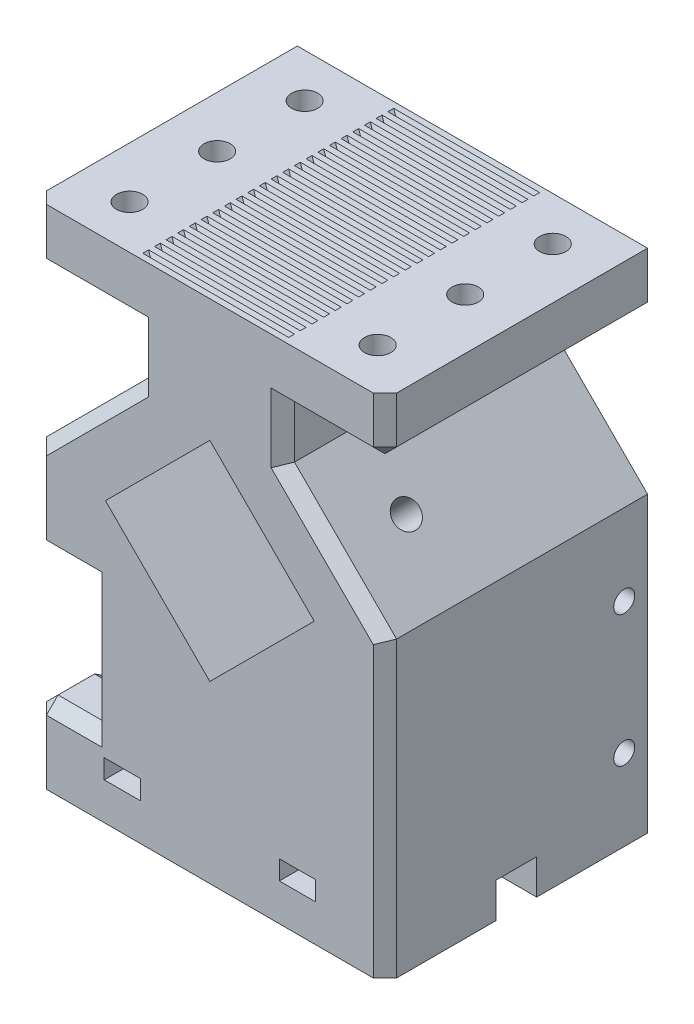
SolidWorks part; units mm, degrees
material "ABS"
ref_plane "Front Plane" through (0, 0, 0) normal (0, 0, 1) x (1, 0, 0)
ref_plane "Top Plane" through (0, 0, 0) normal (0, 1, 0) x (1, 0, 0)
ref_plane "Right Plane" through (0, 0, 0) normal (1, 0, 0) x (0, 0, -1)
sketch "Sketch1" plane through (0, 0, 0) normal (0, 0, 1) x (1, 0, 0)
  line L0 (-30, 25.15) -> (-12.5, 42.65)
  line L2 (30, 25.15) -> (30, -25.15)
  line L3 (30, -25.15) -> (-30, -25.15)
  line L4 (-30, 25.15) -> (-30, -25.15)
  line L5 (30, 25.15) -> (-30, -25.15) construction
  line L6 (30, -25.15) -> (-30, 25.15) construction
  line L7 (30, 25.15) -> (12.5, 42.65)
  line L8 (12.5, 42.65) -> (12.5, 51.65)
  line L9 (-12.5, 42.65) -> (-12.5, 51.65)
  line L10 (-12.5, 51.65) -> (12.5, 51.65) construction
  line L11 (-12.5, 51.65) -> (-30, 51.65)
  line L12 (-30, 51.65) -> (-30, 61.65)
  line L13 (-30, 61.65) -> (30, 61.65)
  line L14 (30, 61.65) -> (30, 51.65)
  line L15 (30, 51.65) -> (12.5, 51.65)
  point P0 (0, 0)
  dimension "D1" = 60
  dimension "D2" = 50.3
  dimension "D3" = 17.5
  dimension "D4" = 17.5
  dimension "D5" = 17.5
  dimension "D6" = 17.5
  dimension "D7" = 9
  dimension "D8" = 10
  dimension "D9" = 25.15
extrude "Boss-Extrude1" add sketch "Sketch1" along normal blind 45
sketch "Sketch2" plane through (0, 0, 45) normal (0, 0, 1) x (1, 0, 0)
  line L0 (0, 40.6296) -> (-17.8898, 22.7398)
  line L1 (-17.8898, 22.7398) -> (0, 4.85)
  line L2 (0, 4.85) -> (17.8898, 22.7398)
  line L3 (17.8898, 22.7398) -> (0, 40.6296)
  line L4 (0, 40.6296) -> (0, 0) construction
  line L5 (-30, -25.15) -> (30, -25.15) construction
  dimension "D1" = 25.3
  dimension "D2" = 25.3
  dimension "D3" = 30
extrude "Cut-Extrude1" cut sketch "Sketch2" against normal blind 25
sketch "Sketch3" plane through (0, -25.15, 0) normal (0, -1, 0) x (1, 0, 0)
  line L0 (-30, 26) -> (30, 26)
  line L1 (-30, 45) -> (-30, 0) construction
  line L2 (30, 45) -> (30, 0) construction
  line L3 (30, 26) -> (30, 19)
  line L4 (30, 19) -> (4.5, 19)
  line L5 (4.5, 19) -> (4.5, 3)
  line L6 (4.5, 3) -> (-4.5, 3)
  line L7 (-4.5, 3) -> (-4.5, 19)
  line L8 (-4.5, 19) -> (-30, 19)
  line L9 (-30, 19) -> (-30, 26)
  line L10 (0, 0) -> (0, 45) construction
  line L11 (-30, 0) -> (30, 0) construction
  line L12 (-30, 45) -> (30, 45) construction
  point P17 (0, 3)
  dimension "D1" = 9
  dimension "D2" = 7
  dimension "D3" = 16
  dimension "D4" = 19
extrude "Cut-Extrude2" cut sketch "Sketch3" against normal blind 6
sketch "Sketch4" plane through (-30, 0, 0) normal (-1, 0, 0) x (0, 0, 1)
  line L0 (45, 25.15) -> (45, -25.15) construction
  line L1 (45, 9.85) -> (28.5, 9.85)
  line L2 (45, 9.85) -> (45, -12.15)
  line L3 (45, -12.15) -> (36.75, -12.15)
  line L5 (45, -25.15) -> (26, -25.15) construction
  line L6 (26, -19.15) -> (36.75, -12.15)
  line L7 (19, -19.15) -> (28.5, 9.85)
  line L8 (26, -19.15) -> (19, -19.15)
  dimension "D1" = 16.5
  dimension "D2" = 13
  dimension "D3" = 22
  dimension "D4" = 8.25
extrude "Cut-Extrude4" cut sketch "Sketch4" against normal blind 9.5
sketch "Sketch5" plane through (0, 0, 0) normal (1, 0, 0) x (0, 0, -1)
  line L0 (-3, -19.15) -> (-3, 9.5665)
  line L1 (-4.0851, 13.008) -> (-11.2085, 23.1813)
  line L2 (-16.1234, 25.7398) -> (-20, 25.7398)
  line L3 (-20, 40.6296) -> (-20, 22.7398) construction
  line L4 (-20, 25.7398) -> (-20, 19.7398)
  line L5 (-20, 22.7398) -> (-20, 4.85) construction
  line L6 (-20, 19.7398) -> (-19.2468, 19.7398)
  line L7 (-14.3319, 17.1813) -> (-10.0851, 11.1162)
  line L8 (-9, 7.6747) -> (-9, -19.15)
  line L9 (-19, -19.15) -> (-3, -19.15) construction
  line L10 (-9, -19.15) -> (-3, -19.15)
  line L11 (-20, 22.7398) -> (-45, 22.7398) construction
  arc A0 (-3, 9.5665) -> (-4.0851, 13.008) centre (-9, 9.5665) ccw
  arc A1 (-10.0851, 11.1162) -> (-9, 7.6747) centre (-15, 7.6747) cw
  arc A2 (-11.2085, 23.1813) -> (-16.1234, 25.7398) centre (-16.1234, 19.7398) ccw
  arc A3 (-19.2468, 19.7398) -> (-14.3319, 17.1813) centre (-19.2468, 13.7398) cw
  point P15 (-19.6234, 19.7398)
  point P24 (-13, 25.7398)
  dimension "D7" = 6
  dimension "D1" = 6
  dimension "D2" = 6
  dimension "D3" = 6
  dimension "D4" = 3
  dimension "D5" = 145
  dimension "D6" = 7
extrude "Cut-Extrude5" cut sketch "Sketch5" against normal mid plane 9
fillet "Fillet1" radius 6 1 edges at (0, -19.15, 9)
ref_plane "Plane1" through (11.5, 0, 0) normal (1, 0, 0) x (0, 0, -1)
sketch "Sketch7" plane through (11.5, 0, 0) normal (1, 0, 0) x (0, 0, -1)
  line L0 (-1, 61.65) -> (-2, 61.65)
  line L1 (-45, 61.65) -> (0, 61.65) construction
  line L2 (-2, 61.65) -> (-1.5, 60.65)
  line L3 (-1.5, 60.65) -> (-1, 61.65)
  line L4 (-1.5, 60.65) -> (-1.5, 61.65) construction
  line L5 (-4, 61.65) -> (-3.5, 60.65)
  line L6 (-3, 61.65) -> (-4, 61.65)
  line L7 (-3.5, 60.65) -> (-3, 61.65)
  line L8 (-6, 61.65) -> (-5.5, 60.65)
  line L9 (-5, 61.65) -> (-6, 61.65)
  line L10 (-5.5, 60.65) -> (-5, 61.65)
  line L11 (-8, 61.65) -> (-7.5, 60.65)
  line L12 (-7, 61.65) -> (-8, 61.65)
  line L13 (-7.5, 60.65) -> (-7, 61.65)
  line L14 (-10, 61.65) -> (-9.5, 60.65)
  line L15 (-9, 61.65) -> (-10, 61.65)
  line L16 (-9.5, 60.65) -> (-9, 61.65)
  line L17 (-12, 61.65) -> (-11.5, 60.65)
  line L18 (-11, 61.65) -> (-12, 61.65)
  line L19 (-11.5, 60.65) -> (-11, 61.65)
  line L20 (-14, 61.65) -> (-13.5, 60.65)
  line L21 (-13, 61.65) -> (-14, 61.65)
  line L22 (-13.5, 60.65) -> (-13, 61.65)
  line L23 (-16, 61.65) -> (-15.5, 60.65)
  line L24 (-15, 61.65) -> (-16, 61.65)
  line L25 (-15.5, 60.65) -> (-15, 61.65)
  line L26 (-18, 61.65) -> (-17.5, 60.65)
  line L27 (-17, 61.65) -> (-18, 61.65)
  line L28 (-17.5, 60.65) -> (-17, 61.65)
  line L29 (-20, 61.65) -> (-19.5, 60.65)
  line L30 (-19, 61.65) -> (-20, 61.65)
  line L31 (-19.5, 60.65) -> (-19, 61.65)
  line L32 (-22, 61.65) -> (-21.5, 60.65)
  line L33 (-21, 61.65) -> (-22, 61.65)
  line L34 (-21.5, 60.65) -> (-21, 61.65)
  line L35 (-24, 61.65) -> (-23.5, 60.65)
  line L36 (-23, 61.65) -> (-24, 61.65)
  line L37 (-23.5, 60.65) -> (-23, 61.65)
  line L38 (-26, 61.65) -> (-25.5, 60.65)
  line L39 (-25, 61.65) -> (-26, 61.65)
  line L40 (-25.5, 60.65) -> (-25, 61.65)
  line L41 (-28, 61.65) -> (-27.5, 60.65)
  line L42 (-27, 61.65) -> (-28, 61.65)
  line L43 (-27.5, 60.65) -> (-27, 61.65)
  line L44 (-30, 61.65) -> (-29.5, 60.65)
  line L45 (-29, 61.65) -> (-30, 61.65)
  line L46 (-29.5, 60.65) -> (-29, 61.65)
  line L47 (-32, 61.65) -> (-31.5, 60.65)
  line L48 (-31, 61.65) -> (-32, 61.65)
  line L49 (-31.5, 60.65) -> (-31, 61.65)
  line L50 (-34, 61.65) -> (-33.5, 60.65)
  line L51 (-33, 61.65) -> (-34, 61.65)
  line L52 (-33.5, 60.65) -> (-33, 61.65)
  line L53 (-36, 61.65) -> (-35.5, 60.65)
  line L54 (-35, 61.65) -> (-36, 61.65)
  line L55 (-35.5, 60.65) -> (-35, 61.65)
  line L56 (-38, 61.65) -> (-37.5, 60.65)
  line L57 (-37, 61.65) -> (-38, 61.65)
  line L58 (-37.5, 60.65) -> (-37, 61.65)
  line L59 (-40, 61.65) -> (-39.5, 60.65)
  line L60 (-39, 61.65) -> (-40, 61.65)
  line L61 (-39.5, 60.65) -> (-39, 61.65)
  line L62 (-42, 61.65) -> (-41.5, 60.65)
  line L63 (-41, 61.65) -> (-42, 61.65)
  line L64 (-41.5, 60.65) -> (-41, 61.65)
  line L65 (-44, 61.65) -> (-43.5, 60.65)
  line L66 (-43, 61.65) -> (-44, 61.65)
  line L67 (-43.5, 60.65) -> (-43, 61.65)
  dimension "D1" = 1
  dimension "D2" = 1
  dimension "D3" = 1
  dimension "D4" = 22
extrude "Cut-Extrude7" cut sketch "Sketch7" against normal blind 23
chamfer "Chamfer1" distance 1 angle 45 44 edges at (-11.5, 61.65, 43.5) (-11.5, 61.65, 41.5) (-11.5, 61.65, 39.5) (-11.5, 61.65, 37.5) (-11.5, 61.65, 35.5) (-11.5, 61.65, 33.5) (-11.5, 61.65, 31.5) (-11.5, 61.65, 29.5) (-11.5, 61.65, 27.5) (-11.5, 61.65, 25.5) (-11.5, 61.65, 23.5) (-11.5, 61.65, 21.5) (-11.5, 61.65, 19.5) (-11.5, 61.65, 17.5) (-11.5, 61.65, 15.5) (-11.5, 61.65, 13.5) (-11.5, 61.65, 11.5) (-11.5, 61.65, 9.5) (-11.5, 61.65, 7.5) (-11.5, 61.65, 5.5) (-11.5, 61.65, 3.5) (-11.5, 61.65, 1.5) (11.5, 61.65, 43.5) (11.5, 61.65, 41.5) (11.5, 61.65, 39.5) (11.5, 61.65, 37.5) (11.5, 61.65, 35.5) (11.5, 61.65, 33.5) (11.5, 61.65, 31.5) (11.5, 61.65, 29.5) (11.5, 61.65, 27.5) (11.5, 61.65, 25.5) (11.5, 61.65, 23.5) (11.5, 61.65, 21.5) (11.5, 61.65, 19.5) (11.5, 61.65, 17.5) (11.5, 61.65, 15.5) (11.5, 61.65, 13.5) (11.5, 61.65, 11.5) (11.5, 61.65, 9.5) (11.5, 61.65, 7.5) (11.5, 61.65, 5.5) (11.5, 61.65, 3.5) (11.5, 61.65, 1.5)
sketch "Sketch8" plane through (0, 61.65, 0) normal (0, 1, 0) x (1, 0, 0)
  line L0 (0, 0) -> (0, -45) construction
  line L1 (30, -45) -> (-30, -45) construction
  line L3 (21.25, -7.5) -> (-21.25, -7.5) construction
  line L4 (21.25, -7.5) -> (21.25, -37.5) construction
  line L5 (21.25, -37.5) -> (-21.25, -37.5) construction
  line L6 (-21.25, -7.5) -> (-21.25, -37.5) construction
  line L7 (21.25, -7.5) -> (-21.25, -37.5) construction
  line L8 (21.25, -37.5) -> (-21.25, -7.5) construction
  circle A0 centre (-21.25, -37.5) radius 2.25
  circle A1 centre (-21.25, -22.5) radius 2.25
  circle A2 centre (-21.25, -7.5) radius 2.25
  circle A3 centre (21.25, -7.5) radius 2.25
  circle A4 centre (21.25, -22.5) radius 2.25
  circle A5 centre (21.25, -37.5) radius 2.25
  point P5 (0, -22.5)
  dimension "D3" = 4.5
  dimension "D4" = 4.5
  dimension "D5" = 4.5
  dimension "D6" = 4.5
  dimension "D7" = 4.5
  dimension "D8" = 4.5
  dimension "D1" = 30
  dimension "D2" = 42.5
extrude "Cut-Extrude8" cut sketch "Sketch8" against normal blind 10
sketch "Sketch9" plane through (0, 51.65, 0) normal (0, -1, 0) x (1, 0, 0)
  line L1 (-25.2915, 22.5) -> (-23.2707, 19)
  line L2 (-23.2707, 19) -> (-19.2293, 19)
  line L3 (-19.2293, 19) -> (-17.2085, 22.5)
  line L4 (-17.2085, 22.5) -> (-19.2293, 26)
  line L5 (-19.2293, 26) -> (-23.2707, 26)
  line L6 (-23.2707, 26) -> (-25.2915, 22.5)
  line L7 (-25.2915, 37.5) -> (-23.2707, 34)
  line L8 (-23.2707, 34) -> (-19.2293, 34)
  line L9 (-19.2293, 34) -> (-17.2085, 37.5)
  line L10 (-17.2085, 37.5) -> (-19.2293, 41)
  line L11 (-19.2293, 41) -> (-23.2707, 41)
  line L12 (-23.2707, 41) -> (-25.2915, 37.5)
  line L13 (-25.2915, 7.5) -> (-23.2707, 4)
  line L14 (-23.2707, 4) -> (-19.2293, 4)
  line L15 (-19.2293, 4) -> (-17.2085, 7.5)
  line L16 (-17.2085, 7.5) -> (-19.2293, 11)
  line L17 (-19.2293, 11) -> (-23.2707, 11)
  line L18 (-23.2707, 11) -> (-25.2915, 7.5)
  line L19 (25.2915, 7.5) -> (23.2707, 11)
  line L20 (23.2707, 11) -> (19.2293, 11)
  line L21 (19.2293, 11) -> (17.2085, 7.5)
  line L22 (17.2085, 7.5) -> (19.2293, 4)
  line L23 (19.2293, 4) -> (23.2707, 4)
  line L24 (23.2707, 4) -> (25.2915, 7.5)
  line L25 (25.4834, 22.6108) -> (23.4627, 26.1108)
  line L26 (23.4627, 26.1108) -> (19.4212, 26.1108)
  line L27 (19.4212, 26.1108) -> (17.4005, 22.6108)
  line L28 (17.4005, 22.6108) -> (19.4212, 19.1108)
  line L29 (19.4212, 19.1108) -> (23.4627, 19.1108)
  line L30 (23.4627, 19.1108) -> (25.4834, 22.6108)
  line L31 (25.4834, 37.6108) -> (23.4627, 41.1108)
  line L32 (23.4627, 41.1108) -> (19.4212, 41.1108)
  line L33 (19.4212, 41.1108) -> (17.4005, 37.6108)
  line L34 (17.4005, 37.6108) -> (19.4212, 34.1108)
  line L35 (19.4212, 34.1108) -> (23.4627, 34.1108)
  line L36 (23.4627, 34.1108) -> (25.4834, 37.6108)
  circle A0 centre (-21.25, 22.5) radius 3.5 construction
  circle A1 centre (-21.25, 37.5) radius 3.5 construction
  circle A2 centre (-21.25, 7.5) radius 3.5 construction
  circle A3 centre (21.25, 7.5) radius 3.5 construction
  circle A4 centre (21.4419, 22.6108) radius 3.5 construction
  circle A5 centre (21.4419, 37.6108) radius 3.5 construction
  dimension "D1" = 7
  dimension "D2" = 7
  dimension "D3" = 7
  dimension "D4" = 7
  dimension "D5" = 7
  dimension "D6" = 7
extrude "Cut-Extrude9" cut sketch "Sketch9" against normal blind 3.2
sketch "Sketch10" plane through (0, -25.15, 0) normal (0, -1, 0) x (1, 0, 0)
  line L0 (-30, 45) -> (-30, 26) construction
  line L1 (15, 7.5) -> (-15, 7.5) construction
  line L2 (15, 7.5) -> (15, 37.5) construction
  line L3 (15, 37.5) -> (-15, 37.5) construction
  line L4 (-15, 7.5) -> (-15, 37.5) construction
  line L5 (15, 7.5) -> (-15, 37.5) construction
  line L6 (15, 37.5) -> (-15, 7.5) construction
  line L7 (-30, 45) -> (30, 45) construction
  circle A0 centre (-15, 37.5) radius 1.75
  circle A1 centre (-15, 7.5) radius 1.75
  circle A2 centre (15, 7.5) radius 1.75
  circle A3 centre (15, 37.5) radius 1.75
  point P0 (0, 22.5)
  dimension "D5" = 3.5
  dimension "D6" = 3.5
  dimension "D7" = 3.5
  dimension "D8" = 3.5
  dimension "D1" = 30
  dimension "D2" = 22.5
  dimension "D3" = 30
  dimension "D4" = 30
extrude "Cut-Extrude10" cut sketch "Sketch10" against normal blind 20
ref_plane "Plane2" through (0, -18.8, 0) normal (0, -1, 0) x (-1, 0, 0)
sketch "Sketch11" plane through (0, -18.8, 0) normal (0, -1, 0) x (-1, 0, 0)
  line L0 (30, -45) -> (-30, -45) construction
  line L1 (-11.9, -45) -> (-18.1, -45)
  line L2 (-11.9, -45) -> (-11.9, -33)
  line L3 (-11.9, -33) -> (-18.1, -33)
  line L4 (-18.1, -45) -> (-18.1, -33)
  line L5 (30, 0) -> (-30, 0) construction
  line L6 (11.9, -45) -> (18.1, -45)
  line L7 (11.9, -45) -> (11.9, -33)
  line L8 (11.9, -33) -> (18.1, -33)
  line L9 (18.1, -45) -> (18.1, -33)
  line L10 (11.9, 0) -> (18.1, 0)
  line L11 (11.9, 0) -> (11.9, -12)
  line L12 (11.9, -12) -> (18.1, -12)
  line L13 (18.1, 0) -> (18.1, -12)
  line L14 (-30, -45) -> (-30, -26) construction
  line L15 (-18.1, 0) -> (-11.9, 0)
  line L16 (-18.1, 0) -> (-18.1, -12)
  line L17 (-18.1, -12) -> (-11.9, -12)
  line L18 (-11.9, 0) -> (-11.9, -12)
  line L19 (30, -45) -> (30, -26) construction
  dimension "D1" = 11.9
  dimension "D2" = 6.2
  dimension "D3" = 12
  dimension "D4" = 11.9
  dimension "D5" = 6.2
  dimension "D6" = 12
extrude "Cut-Extrude11" cut sketch "Sketch11" against normal blind 3.3
sketch "Sketch12" plane through (0, -18.8, 0) normal (0, -1, 0) x (-1, 0, 0)
  line L0 (-15, -7.5) -> (-15, -4.0359) construction
  line L1 (15, -34.0359) -> (12, -35.7679)
  line L2 (12, -35.7679) -> (12, -39.2321)
  line L3 (12, -39.2321) -> (15, -40.9641)
  line L4 (15, -40.9641) -> (18, -39.2321)
  line L5 (18, -39.2321) -> (18, -35.7679)
  line L6 (18, -35.7679) -> (15, -34.0359)
  line L7 (15, -10.9641) -> (18, -9.2321)
  line L8 (18, -9.2321) -> (18, -5.7679)
  line L9 (18, -5.7679) -> (15, -4.0359)
  line L10 (15, -4.0359) -> (12, -5.7679)
  line L11 (12, -5.7679) -> (12, -9.2321)
  line L12 (12, -9.2321) -> (15, -10.9641)
  line L13 (-15, -10.9641) -> (-12, -9.2321)
  line L14 (-12, -9.2321) -> (-12, -5.7679)
  line L15 (-12, -5.7679) -> (-15, -4.0359)
  line L16 (-15, -4.0359) -> (-18, -5.7679)
  line L17 (-18, -5.7679) -> (-18, -9.2321)
  line L18 (-18, -9.2321) -> (-15, -10.9641)
  line L19 (-15, -34.0359) -> (-18, -35.7679)
  line L20 (-18, -35.7679) -> (-18, -39.2321)
  line L21 (-18, -39.2321) -> (-15, -40.9641)
  line L22 (-15, -40.9641) -> (-12, -39.2321)
  line L23 (-12, -39.2321) -> (-12, -35.7679)
  line L24 (-12, -35.7679) -> (-15, -34.0359)
  line L25 (15, -7.5) -> (15, -4.0359) construction
  line L26 (-15, -37.5) -> (-15, -34.0359) construction
  line L27 (15, -37.5) -> (15, -34.0359) construction
  circle A0 centre (15, -37.5) radius 3 construction
  circle A1 centre (15, -7.5) radius 3 construction
  circle A2 centre (-15, -7.5) radius 3 construction
  circle A3 centre (-15, -37.5) radius 3 construction
  dimension "D1" = 6
  dimension "D2" = 6
  dimension "D3" = 6
  dimension "D4" = 6
extrude "Cut-Extrude12" cut sketch "Sketch12" along normal blind 1.5
sketch "Sketch13" plane through (-20.5, 0, 0) normal (-1, 0, 0) x (0, 0, 1)
  line L0 (41, -5.9) -> (41, 3.6) construction
  line L1 (45, -12.15) -> (45, 9.85) construction
  line L2 (36.75, -12.15) -> (45, -12.15) construction
  circle A0 centre (41, -5.9) radius 1.5
  circle A1 centre (41, 3.6) radius 1.5
  dimension "D4" = 3
  dimension "D5" = 3
  dimension "D1" = 4
  dimension "D2" = 9.5
  dimension "D3" = 6.25
extrude "Cut-Extrude13" cut sketch "Sketch13" against normal blind 15
sketch "Sketch14" plane through (-27.575, 27.575, 0) normal (-0.7071, 0.7071, 0) x (0, 0, 1)
  line L0 (45, 21.3193) -> (45, -3.4295) construction
  line L1 (45, -3.4295) -> (0, -3.4295) construction
  circle A0 centre (32.5, 9.0705) radius 2.25
  dimension "D1" = 12.5
  dimension "D2" = 12.5
  dimension "D3" = 4.5
extrude "Cut-Extrude14" cut sketch "Sketch14" against normal blind 15
sketch "Sketch15" plane through (-20.3148, 20.3148, 0) normal (0.7071, -0.7071, 0) x (0, 0, -1)
  line L0 (-32.5, 9.0705) -> (-28.4585, 9.0705) construction
  line L1 (-28.4585, 9.0705) -> (-30.4793, 12.5705)
  line L2 (-30.4793, 12.5705) -> (-34.5207, 12.5705)
  line L3 (-34.5207, 12.5705) -> (-36.5415, 9.0705)
  line L4 (-36.5415, 9.0705) -> (-34.5207, 5.5705)
  line L5 (-34.5207, 5.5705) -> (-30.4793, 5.5705)
  line L6 (-30.4793, 5.5705) -> (-28.4585, 9.0705)
  circle A0 centre (-32.5, 9.0705) radius 3.5 construction
  dimension "D1" = 7
extrude "Cut-Extrude15" cut sketch "Sketch15" against normal blind 3.5
mirror "Mirror1" about plane through (0, 0, 0) normal (1, 0, 0) of "Cut-Extrude14", "Cut-Extrude15"
sketch "Sketch16" plane through (30, 0, 0) normal (1, 0, 0) x (0, 0, -1)
  line L0 (-4, 11.25) -> (-4, -11.25) construction
  line L1 (-19, -25.15) -> (0, -25.15) construction
  line L2 (0, -25.15) -> (0, 25.15) construction
  circle A0 centre (-4, 11.25) radius 1.8
  circle A1 centre (-4, -11.25) radius 1.8
  dimension "D4" = 3.6
  dimension "D5" = 3.6
  dimension "D1" = 13.9
  dimension "D2" = 22.5
  dimension "D3" = 4
extrude "Cut-Extrude23" cut sketch "Sketch16" against normal blind 20
sketch "Sketch17" plane through (0, 0, 0) normal (0, 0, -1) x (-1, 0, 0)
  line L0 (30, -25.15) -> (-30, -25.15) construction
  line L1 (-23.65, -8.15) -> (-20.35, -8.15)
  line L2 (-23.65, -8.15) -> (-23.65, -14.35)
  line L3 (-23.65, -14.35) -> (-20.35, -14.35)
  line L4 (-20.35, -8.15) -> (-20.35, -14.35)
  line L5 (-23.65, 14.35) -> (-20.35, 14.35)
  line L6 (-23.65, 14.35) -> (-23.65, 8.15)
  line L7 (-23.65, 8.15) -> (-20.35, 8.15)
  line L8 (-20.35, 14.35) -> (-20.35, 8.15)
  line L9 (-30, -25.15) -> (-30, 25.15) construction
  point P12 (-22, -8.15)
  dimension "D1" = 10.8
  dimension "D2" = 6.35
  dimension "D3" = 6.2
  dimension "D4" = 6.2
  dimension "D5" = 3.3
  dimension "D6" = 16.3
extrude "Cut-Extrude24" cut sketch "Sketch17" against normal blind 8
sketch "Sketch18" plane through (23.65, 0, 0) normal (-1, 0, 0) x (0, 0, 1)
  line L0 (0.8246, -11.25) -> (4.1512, -11.25) construction
  line L1 (0.8246, 11.25) -> (2.4123, 8.5)
  line L2 (2.4123, 8.5) -> (5.5877, 8.5)
  line L3 (5.5877, 8.5) -> (7.1754, 11.25)
  line L4 (7.1754, 11.25) -> (5.5877, 14)
  line L5 (5.5877, 14) -> (2.4123, 14)
  line L6 (2.4123, 14) -> (0.8246, 11.25)
  line L7 (0.8246, -11.25) -> (2.4123, -14)
  line L8 (2.4123, -14) -> (5.5877, -14)
  line L9 (5.5877, -14) -> (7.1754, -11.25)
  line L10 (7.1754, -11.25) -> (5.5877, -8.5)
  line L11 (5.5877, -8.5) -> (2.4123, -8.5)
  line L12 (2.4123, -8.5) -> (0.8246, -11.25)
  line L13 (4, 11.25) -> (1.0281, 11.25) construction
  circle A0 centre (4, 11.25) radius 2.75 construction
  circle A1 centre (4, -11.25) radius 2.75 construction
  dimension "D1" = 5.5
  dimension "D2" = 5.5
extrude "Cut-Extrude25" cut sketch "Sketch18" against normal blind 1.5
chamfer "Chamfer2" distance 2 angle 45 23 edges at (-30, -25.15, 35.5) (-30, -22.15, 26) (-30, -15.65, 31.375) (-30, -12.15, 40.875) (-30, -18.65, 45) (-30, -22.15, 19) (-30, -4.65, 23.75) (-30, 9.85, 36.75) (-25.25, -12.15, 45) (-20.5, -1.15, 45) (-25.25, 9.85, 45) (-30, 17.5, 45) (-30, 51.65, 22.5) (-21.25, 33.9, 45) (-12.5, 47.15, 45) (-21.25, 51.65, 45) (-30, 56.65, 45) (30, 0, 45) (21.25, 33.9, 45) (12.5, 47.15, 45) (21.25, 51.65, 45) (30, 56.65, 45) (30, 51.65, 22.5)
